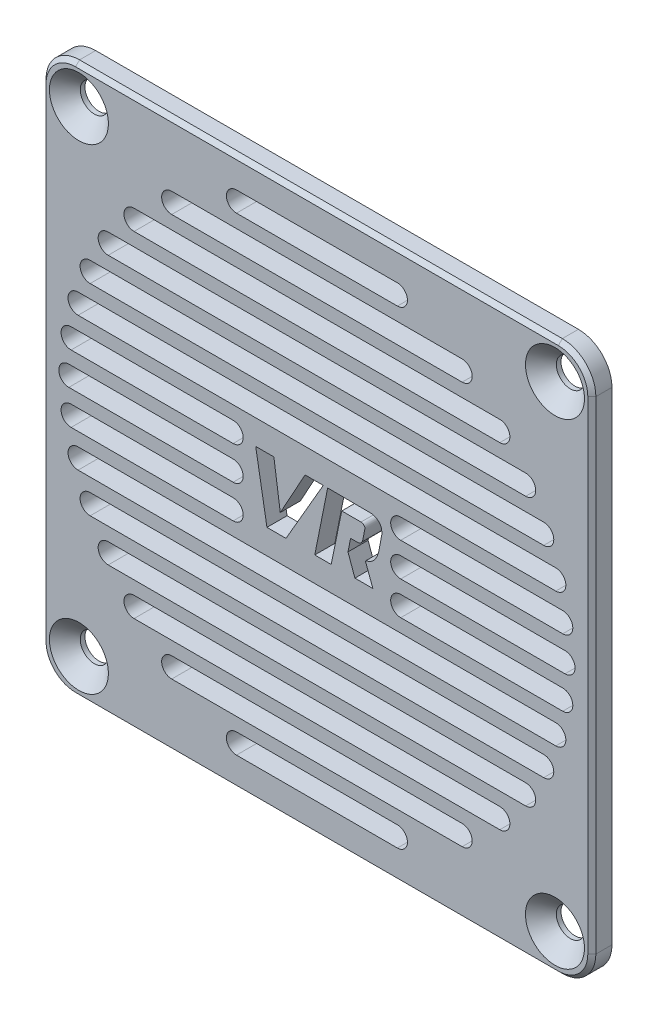
SolidWorks part; units mm, degrees
material "PET-G"
ref_plane "Front Plane" through (0, 0, 0) normal (0, 0, 1) x (1, 0, 0)
ref_plane "Top Plane" through (0, 0, 0) normal (0, 1, 0) x (1, 0, 0)
ref_plane "Right Plane" through (0, 0, 0) normal (1, 0, 0) x (0, 0, -1)
sketch "Sketch1" plane through (0, 0, 0) normal (0, 0, 1) x (1, 0, 0)
  line L0 (41, 36) -> (41, -36)
  line L1 (36, -41) -> (-36, -41)
  line L2 (-41, -36) -> (-41, 36)
  line L3 (-36, 41) -> (36, 41)
  line L4 (0, 6.288) -> (0, 0) construction
  line L5 (0, 0) -> (5.6688, 0) construction
  line L6 (102.5259, 3.6525) -> (240.1283, 3.6525) construction
  line L7 (237.3735, 205.8696) -> (682.0402, 205.8696) construction
  line L8 (155.5388, 233.4582) -> (600.2055, 233.4582) construction
  circle A0 centre (0, 0) radius 10.5 construction
  circle A3 centre (35.5, -35.5) radius 2.1
  circle A4 centre (-35.5, -35.5) radius 2.1
  circle A5 centre (-35.5, 35.5) radius 2.1
  circle A6 centre (35.5, 35.5) radius 2.1
  arc A7 (41, 36) -> (36, 41) centre (36, 36) ccw
  arc A8 (36, -41) -> (41, -36) centre (36, -36) ccw
  arc A9 (-41, -36) -> (-36, -41) centre (-36, -36) ccw
  arc A10 (-36, 41) -> (-41, 36) centre (-36, 36) ccw
  circle A11 centre (0, 0) radius 19.5 construction
  dimension "D1" = 39
  dimension "D2" = 21
  dimension "D5" = 5
  dimension "D6" = 4.2
  dimension "D3" = 82
  dimension "D4" = 82
  dimension "D7" = 71
  dimension "D8" = 71
extrude "Base" add sketch "Sketch1" along normal blind 3 contours L3 A10 L2 A9 L1 A8 L0 A7 A3 A4 A5 A6 region at (0, 0, 0)
chamfer "ScrewChamfer" distance 2.3 angle 45 4 edges at (37.6, -35.5, 3) (-33.4, -35.5, 3) (37.6, 35.5, 3) (-33.4, 35.5, 3)
sketch "Sketch3" plane through (0, 0, 3) normal (0, 0, 1) x (1, 0, 0)
  circle A0 centre (0, 0) radius 10.5 construction
  line B0 (0.9438, 4.8073) -> (-1.7703, 4.8073)
  line B1 (3.7035, 2.8898) -> (6.5735, 2.8898)
  line B2 (6.5735, 2.8898) -> (6.8393, 2.8463) construction
  line B3 (6.8393, 2.8463) -> (7.0318, 2.6813) construction
  line B4 (7.0318, 2.6813) -> (7.1365, 2.5072) construction
  line B5 (7.1365, 2.5072) -> (7.1365, 2.2404) construction
  line B6 (5.021, 0.0136) -> (6.1671, 0.0136)
  line B7 (6.1671, 0.0136) -> (6.4334, 0.0999) construction
  line B8 (6.4334, 0.0999) -> (6.6026, 0.2489) construction
  line B9 (6.6026, 0.2489) -> (6.7446, 0.4146) construction
  line B10 (6.7446, 0.4146) -> (6.8393, 0.6984) construction
  line B11 (6.8393, 0.6984) -> (7.1365, 2.2404) construction
  line B12 (4.6314, -1.9349) -> (5.021, 0.0136)
  line B13 (-9.1314, 4.8073) -> (-6.4211, 4.8073)
  line B14 (-6.4211, 4.8073) -> (-5.4671, -1.8998)
  line B15 (-5.4671, -1.8998) -> (-1.7703, 4.8073)
  line B16 (0.9438, 4.8073) -> (-4.6161, -4.8111)
  line B17 (-4.6161, -4.8111) -> (-7.4548, -4.8111)
  line B18 (-7.4548, -4.8111) -> (-9.1314, 4.8073)
  line B19 (1.6005, 4.8073) -> (8.0334, 4.7764)
  line B20 (7.2293, -1.8111) -> (8.3427, -4.8111)
  line B21 (8.3427, -4.8111) -> (5.6631, -4.8111)
  line B22 (5.6631, -4.8111) -> (4.6314, -1.9349)
  line B23 (3.7035, 2.8898) -> (2.1262, -4.8111)
  line B24 (2.1262, -4.8111) -> (-0.3232, -4.8111)
  line B25 (-0.3232, -4.8111) -> (1.6005, 4.8073)
  line B26 (9.6784, 2.8463) -> (9.2292, 0.4146)
  spline B27 degree 3 poles (9.2292, 0.4146) (9.1202, 0.0172) (8.9153, -0.5548) (8.4464, -1.1602) (7.9426, -1.5631) (7.4993, -1.705) (7.2293, -1.8111) knots 0 0 0 0 0.394089 0.566272 0.722136 1 1 1 1
  spline B28 degree 3 poles (9.6784, 2.8463) (9.687, 2.9892) (9.6873, 3.2192) (9.6341, 3.5736) (9.531, 3.877) (9.319, 4.175) (9.0589, 4.4168) (8.7482, 4.6112) (8.4048, 4.733) (8.1636, 4.7706) (8.0334, 4.7764) knots 0 0 0 0 0.150298 0.240096 0.375313 0.481557 0.62039 0.745312 0.863341 1 1 1 1
  spline B29 degree 3 poles (6.5735, 2.8898) (6.6399, 2.879) (6.7064, 2.8681) (6.7728, 2.8572) (6.7866, 2.8549) (6.8142, 2.8504) (6.8556, 2.8324) (6.8768, 2.8142) (6.8874, 2.8051) (6.9195, 2.7776) (6.9516, 2.7501) (6.9837, 2.7226) (6.9932, 2.7144) (7.0122, 2.6981) (7.0386, 2.67) (7.0515, 2.6485) (7.058, 2.6378) (7.0754, 2.6088) (7.0929, 2.5797) (7.1103, 2.5507) (7.1168, 2.5399) (7.1298, 2.5183) (7.1365, 2.4782) (7.1365, 2.453) (7.1365, 2.4405) (7.1365, 2.396) (7.1365, 2.3515) (7.1365, 2.3071) (7.1365, 2.2923) (7.1365, 2.2628) (7.1322, 2.2183) (7.1266, 2.1894) (7.1239, 2.1749) (7.0337, 1.7072) (6.9436, 1.2395) (6.8534, 0.7718) (6.8503, 0.7555) (6.844, 0.723) (6.8314, 0.6746) (6.8209, 0.6432) (6.8156, 0.6274) (6.7998, 0.5801) (6.784, 0.5328) (6.7683, 0.4855) (6.7638, 0.4721) (6.7549, 0.4454) (6.7366, 0.4053) (6.7183, 0.3838) (6.7091, 0.3731) (6.6854, 0.3455) (6.6617, 0.3179) (6.6381, 0.2903) (6.6301, 0.2809) (6.6141, 0.2623) (6.5879, 0.236) (6.5695, 0.2197) (6.5603, 0.2116) (6.5321, 0.1868) (6.5039, 0.1619) (6.4757, 0.1371) (6.4653, 0.128) (6.4447, 0.1099) (6.406, 0.091) (6.3799, 0.0825) (6.3668, 0.0783) (6.3002, 0.0567) (6.2336, 0.0352) (6.1671, 0.0136) knots 0 0 0 0 0.056598 0.056598 0.056598 0.068353 0.080109 0.091864 0.091864 0.091864 0.127378 0.127378 0.127378 0.137906 0.148433 0.158961 0.158961 0.158961 0.187427 0.187427 0.187427 0.198008 0.208589 0.21917 0.21917 0.21917 0.256543 0.256543 0.256543 0.268944 0.281346 0.293747 0.293747 0.293747 0.694048 0.694048 0.694048 0.707988 0.721929 0.735869 0.735869 0.735869 0.777781 0.777781 0.777781 0.789642 0.801504 0.813365 0.813365 0.813365 0.843938 0.843938 0.843938 0.854271 0.864604 0.874936 0.874936 0.874936 0.906514 0.906514 0.906514 0.91807 0.929625 0.941181 0.941181 0.941181 1 1 1 1
  dimension "D1" = 21
sketch_block_instance "Block1-1"
sketch_block "Block1" parameters "D1"=1.6237
extrude "Logo" cut sketch "Sketch3" against normal through all
sketch "Sketch4" plane through (0, 0, 3) normal (0, 0, 1) x (1, 0, 0)
  line L0 (-33.8231, 15) -> (33.8231, 15) construction
  line L1 (11, -5.7242) -> (-11, -5.7242) construction
  line L2 (0, 0) -> (-7.3146, 0) construction
  line L3 (11, -5.7242) -> (11, 5.7242) construction
  line L4 (11, 5.7242) -> (-11, 5.7242) construction
  line L5 (-11, -5.7242) -> (-11, 5.7242) construction
  line L6 (11, -5.7242) -> (-11, 5.7242) construction
  line L7 (11, 5.7242) -> (-11, -5.7242) construction
  line L8 (-33.8231, 16.5) -> (33.8231, 16.5)
  line L9 (-33.8231, 13.5) -> (33.8231, 13.5)
  line L10 (-35.623, 10) -> (35.623, 10) construction
  line L11 (-35.623, 11.5) -> (35.623, 11.5)
  line L12 (-35.623, 8.5) -> (35.623, 8.5)
  line L13 (-33.8231, -15) -> (33.8231, -15) construction
  line L14 (-33.8231, -13.5) -> (33.8231, -13.5)
  line L15 (-33.8231, -16.5) -> (33.8231, -16.5)
  line L16 (-35.623, -10) -> (35.623, -10) construction
  line L17 (-35.623, -8.5) -> (35.623, -8.5)
  line L18 (-35.623, -11.5) -> (35.623, -11.5)
  line L19 (12.5, 5) -> (36.6606, 5) construction
  line L20 (12.5, 6.5) -> (36.6606, 6.5)
  line L21 (12.5, 3.5) -> (36.6606, 3.5)
  line L22 (12.5, -5) -> (36.6606, -5) construction
  line L23 (12.5, -3.5) -> (36.6606, -3.5)
  line L24 (12.5, -6.5) -> (36.6606, -6.5)
  line L25 (-36.6606, 5) -> (-12.5, 5) construction
  line L26 (-36.6606, 6.5) -> (-12.5, 6.5)
  line L27 (-36.6606, 3.5) -> (-12.5, 3.5)
  line L28 (-36.6606, -5) -> (-12.5, -5) construction
  line L29 (-36.6606, -3.5) -> (-12.5, -3.5)
  line L30 (-36.6606, -6.5) -> (-12.5, -6.5)
  line L31 (0, 0) -> (0, 7.3736) construction
  line L32 (-37, 0) -> (-12.5, 0) construction
  line L33 (-37, 1.5) -> (-12.5, 1.5)
  line L34 (-37, -1.5) -> (-12.5, -1.5)
  line L35 (12.5, 0) -> (37, 0) construction
  line L36 (12.5, 1.5) -> (37, 1.5)
  line L37 (12.5, -1.5) -> (37, -1.5)
  line L38 (-31.1288, 20) -> (31.1288, 20) construction
  line L39 (-31.1288, 21.5) -> (31.1288, 21.5)
  line L40 (-31.1288, 18.5) -> (31.1288, 18.5)
  line L41 (-27.2764, 25) -> (27.2764, 25) construction
  line L42 (-27.2764, 26.5) -> (27.2764, 26.5)
  line L43 (-27.2764, 23.5) -> (27.2764, 23.5)
  line L44 (-21.6564, 30) -> (21.6564, 30) construction
  line L45 (-21.6564, 31.5) -> (21.6564, 31.5)
  line L46 (-21.6564, 28.5) -> (21.6564, 28.5)
  line L47 (-12, 35) -> (12, 35) construction
  line L48 (-12, 36.5) -> (12, 36.5)
  line L49 (-12, 33.5) -> (12, 33.5)
  line L50 (-31.1288, -20) -> (31.1288, -20) construction
  line L51 (-31.1288, -21.5) -> (31.1288, -21.5)
  line L52 (-31.1288, -18.5) -> (31.1288, -18.5)
  line L53 (-27.2764, -25) -> (27.2764, -25) construction
  line L54 (-27.2764, -26.5) -> (27.2764, -26.5)
  line L55 (-27.2764, -23.5) -> (27.2764, -23.5)
  line L56 (-21.6564, -30) -> (21.6564, -30) construction
  line L57 (-21.6564, -31.5) -> (21.6564, -31.5)
  line L58 (-21.6564, -28.5) -> (21.6564, -28.5)
  line L59 (-12, -35) -> (12, -35) construction
  line L60 (-12, -36.5) -> (12, -36.5)
  line L61 (-12, -33.5) -> (12, -33.5)
  circle A0 centre (0, 0) radius 38.5 construction
  circle A1 centre (0, 0) radius 10.5 construction
  arc A2 (-33.8231, 16.5) -> (-33.8231, 13.5) centre (-33.8231, 15) ccw
  arc A3 (33.8231, 13.5) -> (33.8231, 16.5) centre (33.8231, 15) ccw
  arc A4 (-35.623, 11.5) -> (-35.623, 8.5) centre (-35.623, 10) ccw
  arc A5 (35.623, 8.5) -> (35.623, 11.5) centre (35.623, 10) ccw
  arc A6 (-33.8231, -13.5) -> (-33.8231, -16.5) centre (-33.8231, -15) ccw
  arc A7 (33.8231, -16.5) -> (33.8231, -13.5) centre (33.8231, -15) ccw
  arc A8 (-35.623, -8.5) -> (-35.623, -11.5) centre (-35.623, -10) ccw
  arc A9 (35.623, -11.5) -> (35.623, -8.5) centre (35.623, -10) ccw
  arc A10 (12.5, 6.5) -> (12.5, 3.5) centre (12.5, 5) ccw
  arc A11 (36.6606, 3.5) -> (36.6606, 6.5) centre (36.6606, 5) ccw
  arc A12 (12.5, -3.5) -> (12.5, -6.5) centre (12.5, -5) ccw
  arc A13 (36.6606, -6.5) -> (36.6606, -3.5) centre (36.6606, -5) ccw
  arc A14 (-36.6606, 6.5) -> (-36.6606, 3.5) centre (-36.6606, 5) ccw
  arc A15 (-12.5, 3.5) -> (-12.5, 6.5) centre (-12.5, 5) ccw
  arc A16 (-36.6606, -3.5) -> (-36.6606, -6.5) centre (-36.6606, -5) ccw
  arc A17 (-12.5, -6.5) -> (-12.5, -3.5) centre (-12.5, -5) ccw
  arc A18 (-37, 1.5) -> (-37, -1.5) centre (-37, 0) ccw
  arc A19 (-12.5, -1.5) -> (-12.5, 1.5) centre (-12.5, 0) ccw
  arc A20 (12.5, 1.5) -> (12.5, -1.5) centre (12.5, 0) ccw
  arc A21 (37, -1.5) -> (37, 1.5) centre (37, 0) ccw
  arc A22 (-31.1288, 21.5) -> (-31.1288, 18.5) centre (-31.1288, 20) ccw
  arc A23 (31.1288, 18.5) -> (31.1288, 21.5) centre (31.1288, 20) ccw
  arc A24 (-27.2764, 26.5) -> (-27.2764, 23.5) centre (-27.2764, 25) ccw
  arc A25 (27.2764, 23.5) -> (27.2764, 26.5) centre (27.2764, 25) ccw
  arc A26 (-21.6564, 31.5) -> (-21.6564, 28.5) centre (-21.6564, 30) ccw
  arc A27 (21.6564, 28.5) -> (21.6564, 31.5) centre (21.6564, 30) ccw
  arc A28 (-12, 36.5) -> (-12, 33.5) centre (-12, 35) ccw
  arc A29 (12, 33.5) -> (12, 36.5) centre (12, 35) ccw
  arc A30 (-31.1288, -21.5) -> (-31.1288, -18.5) centre (-31.1288, -20) cw
  arc A31 (31.1288, -18.5) -> (31.1288, -21.5) centre (31.1288, -20) cw
  arc A32 (-27.2764, -26.5) -> (-27.2764, -23.5) centre (-27.2764, -25) cw
  arc A33 (27.2764, -23.5) -> (27.2764, -26.5) centre (27.2764, -25) cw
  arc A34 (-21.6564, -31.5) -> (-21.6564, -28.5) centre (-21.6564, -30) cw
  arc A35 (21.6564, -28.5) -> (21.6564, -31.5) centre (21.6564, -30) cw
  arc A36 (-12, -36.5) -> (-12, -33.5) centre (-12, -35) cw
  arc A37 (12, -33.5) -> (12, -36.5) centre (12, -35) cw
  point P6 (0, 15)
  point P16 (0, 10)
  point P23 (0, -15)
  point P30 (0, -10)
  point P37 (24.5803, 5)
  point P44 (24.5803, -5)
  point P51 (-24.5803, 5)
  point P58 (-24.5803, -5)
  point P68 (0, 20)
  point P71 (-24.75, 0)
  point P78 (24.75, 0)
  point P89 (0, 25)
  point P96 (0, 30)
  point P103 (0, 35)
  point P114 (0, -20)
  point P121 (0, -25)
  point P128 (0, -30)
  point P135 (0, -35)
  point P155 (0, 0)
  dimension "D1" = 77
  dimension "D2" = 21
  dimension "D4" = 3
  dimension "D5" = 3
  dimension "D3" = 22
  dimension "D6" = 3
  dimension "D7" = 3
  dimension "D8" = 3
  dimension "D9" = 3
  dimension "D10" = 2
  dimension "D11" = 2
  dimension "D12" = 2
  dimension "D13" = 2
  dimension "D14" = 2
  dimension "D15" = 2
  dimension "D16" = 2
  dimension "D17" = 2
extrude "Slots" cut sketch "Sketch4" against normal through all contours L9 A3 L8 A2 | L12 A5 L11 A4 | L27 A15 L26 A14 | L30 A17 L29 A16 | L18 A9 L17 A8 | L15 A7 L14 A6 | L24 A13 L23 A12 | L21 A11 L20 A10 | L34 A19 L33 A18 | L37 A21 L36 A20 | L40 A23 L39 A22 | L43 A25 L42 A24 | L46 A27 L45 A26 | L49 A29 L48 A28 | A31 L52 A30 L51 | A33 L55 A32 L54 | A35 L58 A34 L57 | A37 L61 A36 L60
chamfer "OutsideChamfer" distance 0.6 angle 45 8 edges at (0, -41, 3) (-39.5355, -39.5355, 3) (39.5355, -39.5355, 3) (-41, 0, 3) (41, 0, 3) (-39.5355, 39.5355, 3) (39.5355, 39.5355, 3) (0, 41, 3)
equation "\"D4\"=80"
equation "\"D3@Sketch1\"=\"D4@Sketch1\""
